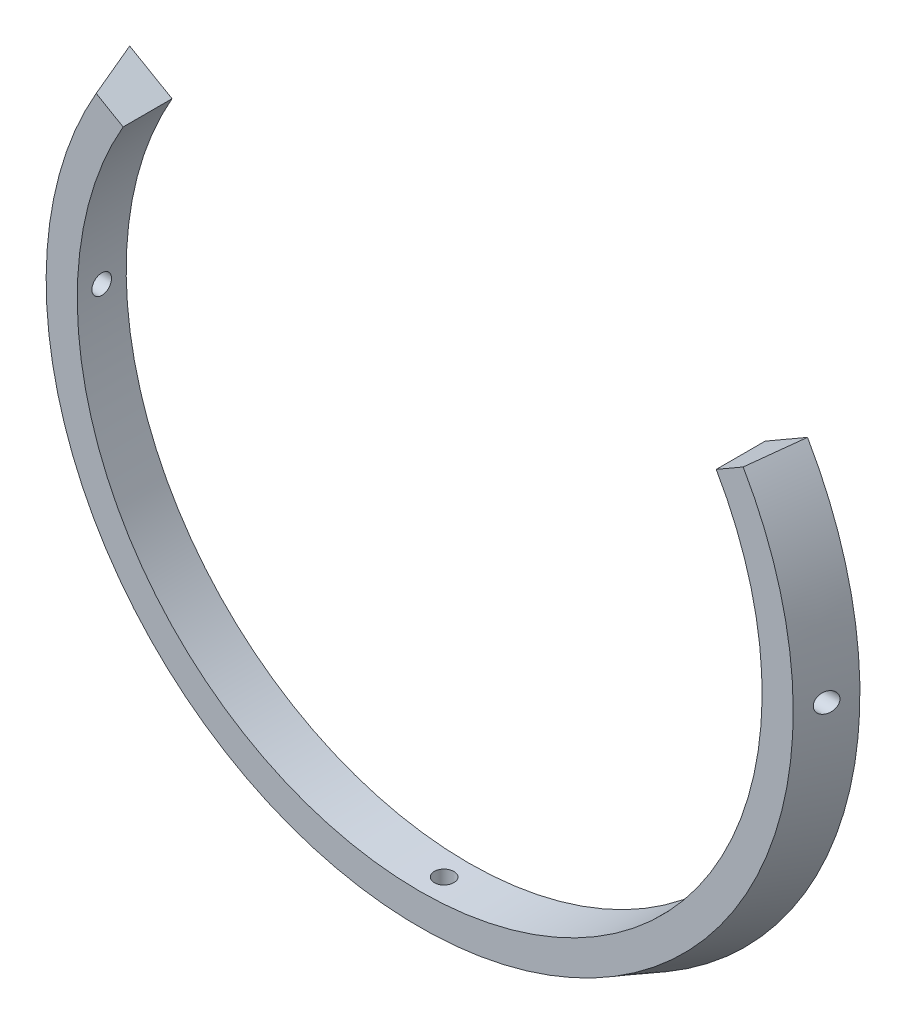
SolidWorks part; units mm, degrees
ref_plane "Piano frontale" through (0, 0, 0) normal (0, 0, 1) x (1, 0, 0)
ref_plane "Piano superiore" through (0, 0, 0) normal (0, 1, 0) x (1, 0, 0)
ref_plane "Piano destro" through (0, 0, 0) normal (1, 0, 0) x (0, 0, -1)
sketch "Schizzo1" plane through (0, 0, 0) normal (0, 0, 1) x (1, 0, 0)
  circle A0 centre (0, 0) radius 80
  circle A1 centre (0, 0) radius 70
  dimension "D1" = 140
  dimension "D2" = 160
extrude "Estrusione-Estrusione1" add sketch "Schizzo1" along normal blind 10
chamfer "Smusso1" distance 10 angle 20 1 edges at (80, 0, 10)
sketch "Schizzo2" plane through (0, 0, 0) normal (0, 1, 0) x (1, 0, 0)
  circle A0 centre (0, -5) radius 2
  point P2 (0, 0)
  dimension "D2" = 4
  dimension "D1" = 5
extrude "Taglio-Estrusione1" cut sketch "Schizzo2" against normal through all
pattern_circular "RipetizioneCircolare1" count 2 every 90 about axis through (0, 0, 0) along (0, 0, 1) of "Taglio-Estrusione1"
sketch "Schizzo3" plane through (0, 0, 0) normal (0, 0, -1) x (-1, 0, 0)
  line L0 (60.6218, 35) -> (69.282, 40)
  line L1 (-60.6218, 35) -> (-69.282, 40)
  line L2 (0, 0) -> (0, 34.8699) construction
  arc A0 (-60.6218, 35) -> (60.6218, 35) centre (0, 0) cw
  circle A1 centre (0, 0) radius 70 construction
  arc A2 (-69.282, 40) -> (69.282, 40) centre (0, 0) cw
  circle A3 centre (0, 0) radius 80 construction
  point P2 (40, 57.4456)
  point P7 (29.7244, 0)
  point P10 (41.6386, 68.3098)
  point P14 (36.5872, -59.6773)
  point P15 (41.378, -69.282)
  point P16 (6.3127, 34.2937)
  dimension "D1" = 60
  dimension "D2" = 60
  dimension "D3" = 10
extrude "Taglio-Estrusione3" cut sketch "Schizzo3" against normal through all
